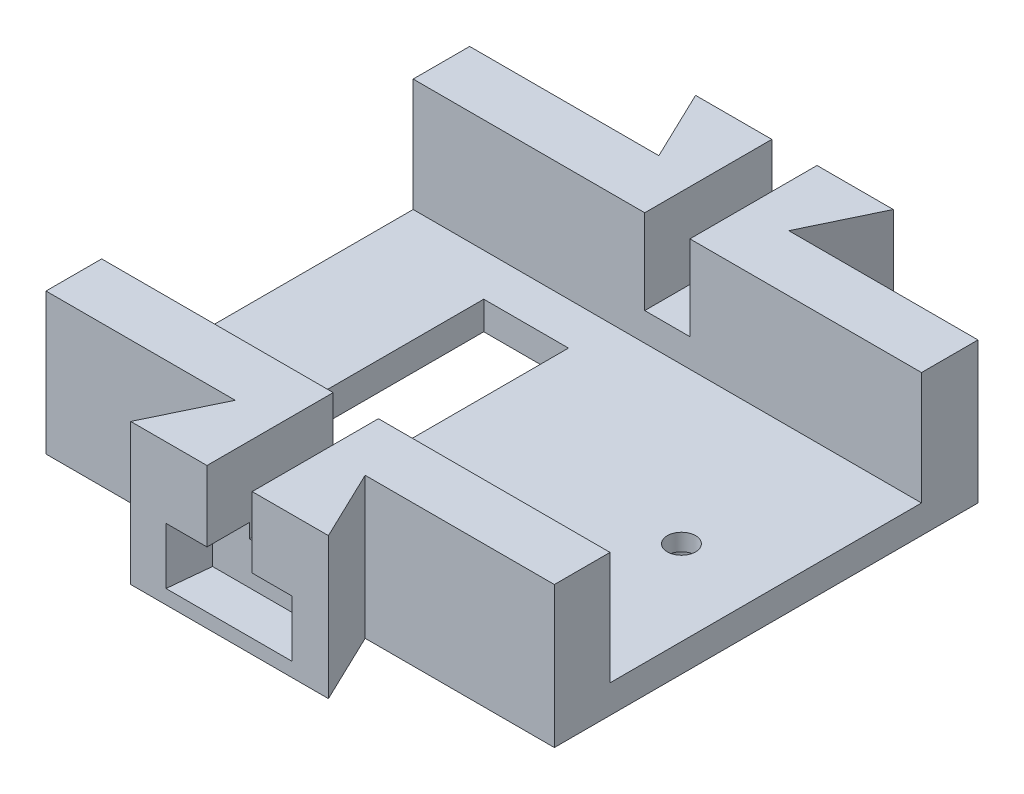
SolidWorks part; units mm, degrees
ref_plane "Front Plane" through (0, 0, 0) normal (0, 0, 1) x (1, 0, 0)
ref_plane "Top Plane" through (0, 0, 0) normal (0, 1, 0) x (1, 0, 0)
ref_plane "Right Plane" through (0, 0, 0) normal (1, 0, 0) x (0, 0, -1)
sketch "Sketch1" plane through (0, 0, 0) normal (0, 1, 0) x (1, 0, 0)
  line L1 (-59.3211, 124.9321) -> (120.6789, 124.9321)
  line L2 (-59.3211, 124.9321) -> (-59.3211, -25.0679)
  line L3 (-59.3211, -25.0679) -> (120.6789, -25.0679)
  line L4 (120.6789, 124.9321) -> (120.6789, -25.0679)
  line L5 (-19.3211, 9.9321) -> (10.6789, 9.9321)
  line L6 (-19.3211, 9.9321) -> (-19.3211, 89.9321)
  line L7 (-19.3211, 89.9321) -> (10.6789, 89.9321)
  line L8 (10.6789, 9.9321) -> (10.6789, 89.9321)
  dimension "D1" = 35
  dimension "D2" = 35
  dimension "D3" = 40
extrude "Boss-Extrude1" add sketch "Sketch1" along normal blind 50
shell "Shell1" thickness 20 removed face at (30.6789, 50, -49.9321)
sketch "Sketch3" plane through (0, 0, 0) normal (0, -1, 0) x (-1, 0, 0)
sketch "Sketch4" plane through (0, 50, 0) normal (0, 1, 0) x (1, 0, 0)
  line L0 (-39.3211, -5.0679) -> (-39.3211, 104.9321)
  line L1 (-39.3211, 104.9321) -> (30.6789, 104.9321)
  line L2 (30.6789, 104.9321) -> (30.6789, -5.0679)
  line L3 (30.6789, -5.0679) -> (-39.3211, -5.0679)
  line L4 (30.6789, -5.0679) -> (100.6789, -5.0679) construction
extrude "Cut-Extrude1" cut sketch "Sketch4" against normal blind 30
sketch "Sketch5" plane through (0, 0, 0) normal (0, -1, 0) x (1, 0, 0)
  line L0 (30.6789, 25.0679) -> (7.6789, 25.0679)
  line L1 (-59.3211, 25.0679) -> (120.6789, 25.0679) construction
  line L2 (7.6789, 25.0679) -> (-4.3211, 50.0679)
  line L3 (-4.3211, 50.0679) -> (65.6789, 50.0679)
  line L4 (65.6789, 50.0679) -> (53.6789, 25.0679)
  line L5 (53.6789, 25.0679) -> (30.6789, 25.0679)
  line L7 (19.067, 29.7324) -> (61.7771, 29.7324)
  line L8 (61.7771, 29.7324) -> (73.0332, 45.955)
  line L9 (73.0332, 45.955) -> (10.5603, 45.955)
  line L10 (10.5603, 45.955) -> (19.067, 29.7324)
  dimension "D1" = 23
  dimension "D2" = 23
  dimension "D3" = 25
  dimension "D4" = 25
  dimension "D5" = 55
  dimension "D6" = 55
extrude "Boss-Extrude2" add sketch "Sketch5" against normal blind 50 contours L3 L4 L5 L0 L2
sketch "Sketch6" plane through (0, 50, 0) normal (0, 1, 0) x (1, 0, 0)
  line L0 (22.6789, -50.0679) -> (22.6789, -5.0679)
  line L1 (-4.3211, -50.0679) -> (65.6789, -50.0679) construction
  line L2 (-39.3211, -5.0679) -> (100.6789, -5.0679) construction
  line L3 (22.6789, -5.0679) -> (38.6789, -5.0679)
  line L4 (38.6789, -5.0679) -> (38.6789, -50.0679)
  line L5 (38.6789, -50.0679) -> (22.6789, -50.0679)
  dimension "D1" = 15
  dimension "D2" = 15
extrude "Cut-Extrude2" cut sketch "Sketch6" against normal blind 30
ref_plane "Plane1" through (0, 0, -49.9321) normal (0, 0, 1) x (1, 0, 0)
sketch "Sketch7" plane through (0, 0, 0) normal (0, -1, 0) x (-1, 0, 0)
  line L0 (-90.6789, 124.9321) -> (-90.6789, -25.0679) construction
  line L1 (-120.6789, 124.9321) -> (59.3211, 124.9321) construction
  line L2 (-53.6789, -25.0679) -> (-120.6789, -25.0679) construction
  line L3 (-90.6789, 49.9321) -> (-120.6789, 49.9321) construction
  line L4 (-120.6789, -25.0679) -> (-120.6789, 124.9321) construction
  circle A0 centre (-90.6789, 49.9321) radius 5
extrude "Cut-Extrude3" cut sketch "Sketch7" against normal blind 28 contours A0
sketch "Sketch8" plane through (120.6789, 0, 0) normal (1, 0, 0) x (0, 0, -1)
  line L0 (104.9321, 50) -> (104.9321, 10)
  line L1 (-25.0679, 50) -> (124.9321, 50) construction
  line L2 (104.9321, 10) -> (-5.3609, 10)
  line L3 (-5.3609, 10) -> (-5.3609, 50)
  line L4 (-5.3609, 50) -> (104.9321, 50)
extrude "Cut-Extrude4" cut sketch "Sketch8" against normal blind 213
sketch "Sketch9" plane through (0, 0, 0) normal (0, -1, 0) x (1, 0, 0)
  line L0 (49.1131, -66.3474) -> (20.5792, -66.3474)
  line L1 (20.5792, -66.3474) -> (29.8654, -57.0611)
  line L2 (29.8654, -57.0611) -> (58.3993, -57.0611)
  line L3 (58.3993, -57.0611) -> (49.1131, -66.3474)
  line L4 (39.3182, -54.9958) -> (39.3182, -45.201)
  line L5 (39.3182, -45.201) -> (48.6045, -35.9147)
  line L6 (48.6045, -35.9147) -> (58.3993, -35.9147)
  line L7 (58.3993, -35.9147) -> (39.3182, -54.9958)
  line L8 (46.3978, -35.9147) -> (29.8654, -35.9147)
  line L9 (29.8654, -35.9147) -> (20.5792, -45.201)
  line L10 (20.5792, -45.201) -> (37.1116, -45.201)
  line L11 (37.1116, -45.201) -> (46.3978, -35.9147)
extrude "Cut-Extrude5" cut sketch "Sketch9" against normal blind 2 contours L7 L6 L5 L4 | L10 L11 L8 L9 | L0 L1 L2 L3 region at (46.6919, 0, -43.2884) region at (33.4885, 0, -40.5578)
sketch "Sketch10" plane through (0, 0, 0) normal (0, -1, 0) x (1, 0, 0)
  circle A0 centre (90.6789, -49.9321) radius 8
  circle A1 centre (90.6789, -49.9321) radius 5 construction
extrude "Cut-Extrude6" cut sketch "Sketch10" against normal blind 4
sketch "Sketch11" plane through (0, 0, 0) normal (0, -1, 0) x (-1, 0, 0)
  line L0 (4.3211, 94.9321) -> (4.3211, 89.9321) construction
  line L1 (24.3211, 94.9321) -> (-15.6789, 94.9321)
  line L2 (24.3211, 94.9321) -> (24.3211, 4.9321)
  line L3 (24.3211, 4.9321) -> (-15.6789, 4.9321)
  line L4 (-15.6789, 94.9321) -> (-15.6789, 4.9321)
  line L5 (-10.6789, 89.9321) -> (19.3211, 89.9321) construction
  line L6 (4.3211, 9.9321) -> (4.3211, 4.9321) construction
  line L7 (19.3211, 9.9321) -> (-10.6789, 9.9321) construction
sketch "Sketch13" plane through (0, 0, 50.0679) normal (0, 0, 1) x (1, 0, 0)
  line L0 (40.9724, 5.0164) -> (40.9724, 25.0164)
  line L1 (40.9724, 25.0164) -> (20.9724, 25.0164)
  line L2 (20.9724, 25.0164) -> (20.9724, 5.0164)
  line L3 (20.9724, 5.0164) -> (40.9724, 5.0164)
extrude "Cut-Extrude10" cut sketch "Sketch13" against normal blind 15
sketch "Sketch14" plane through (0, 0, 0) normal (0, -1, 0) x (-1, 0, 0)
  line L0 (-53.1789, -50.0679) -> (-50.6789, -25.0679)
  line L1 (-50.6789, -25.0679) -> (-10.6789, -25.0679)
  line L2 (-10.6789, -25.0679) -> (-8.1789, -50.0679)
  line L3 (-8.1789, -50.0679) -> (-53.1789, -50.0679)
  line L4 (-50.6789, -25.0679) -> (-53.6789, -25.0679) construction
  line L5 (-7.6789, -25.0679) -> (-10.6789, -25.0679) construction
  line L9 (4.3211, -50.0679) -> (-65.6789, -50.0679) construction
sketch "Sketch16" plane through (0, 25.0164, 0) normal (0, -1, 0) x (1, 0, 0)
  line L0 (9.659, 35.0679) -> (8.159, 50.0679)
  line L1 (8.159, 50.0679) -> (52.7046, 50.0679)
  line L2 (52.7046, 50.0679) -> (51.2046, 35.0679)
  line L3 (51.2046, 35.0679) -> (9.659, 35.0679)
  line L4 (8.159, 50.0679) -> (19.0273, 50.0679) construction
  line L5 (63.5729, 50.0679) -> (52.7046, 50.0679) construction
  line L6 (40.9724, 50.0679) -> (38.6789, 50.0679) construction
  line L7 (22.6789, 35.0679) -> (20.9724, 35.0679) construction
  line L8 (10.6789, 25.0679) -> (8.1789, 50.0679) construction
  point P18 (21.8257, 35.0679)
extrude "Cut-Extrude11" cut sketch "Sketch16" along normal blind 20
mirror "Mirror1" about plane through (0, 0, -49.9321) normal (0, 0, 1) of "Cut-Extrude2", "Cut-Extrude11", "Cut-Extrude10", "Boss-Extrude2"
